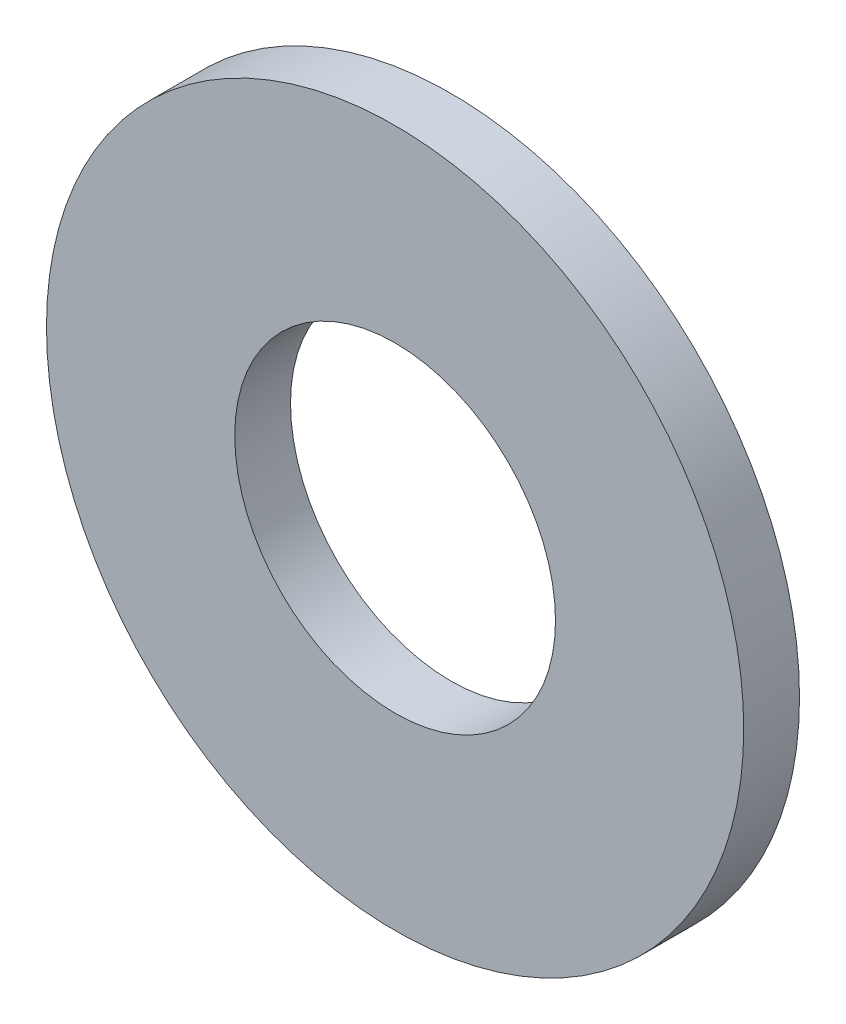
SolidWorks part; units mm, degrees
material "Rubber"
ref_plane "Front Plane" through (0, 0, 0) normal (0, 0, 1) x (1, 0, 0)
ref_plane "Top Plane" through (0, 0, 0) normal (0, 1, 0) x (1, 0, 0)
ref_plane "Right Plane" through (0, 0, 0) normal (1, 0, 0) x (0, 0, -1)
sketch "Sketch1" plane through (0, 0, 0) normal (0, 0, 1) x (1, 0, 0)
  line L0 (0, 0) -> (3.175, -5.4993) construction
  line L1 (0, 0) -> (0, -6.35) construction
  circle A0 centre (0, 0) radius 2.921
  circle A1 centre (0, 0) radius 6.35
  point P4 (0, -2.921)
  point P7 (1.4605, -2.5297)
  dimension "D1" = 30
  dimension "ID" = 5.842
  dimension "OD" = 12.7
extrude "Extrude1" add sketch "Sketch1" against normal blind 1.016
ref_axis "Center Axis 1" through (0, 0, -1.9202) along (0, 0, 1)
